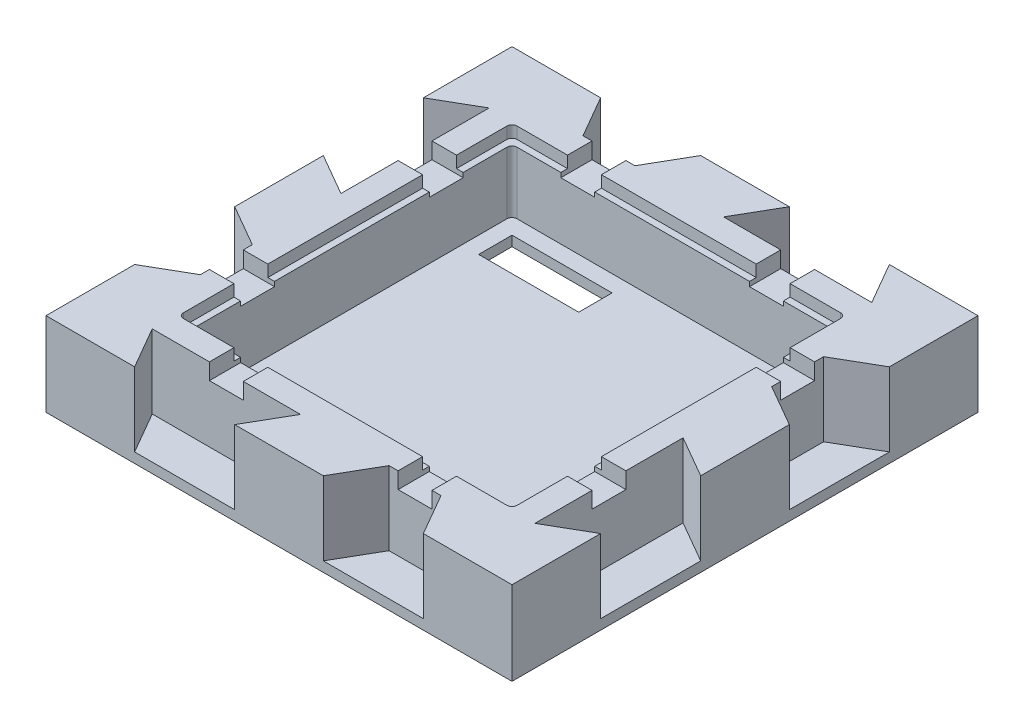
SolidWorks part; units mm, degrees
material "Macor"
ref_plane "Front Plane" through (0, 0, 0) normal (0, 0, 1) x (1, 0, 0)
ref_plane "Top Plane" through (0, 0, 0) normal (0, 1, 0) x (1, 0, 0)
ref_plane "Right Plane" through (0, 0, 0) normal (1, 0, 0) x (0, 0, -1)
sketch "Sketch1" plane through (0, 0, 0) normal (0, 1, 0) x (1, 0, 0)
  line L1 (-69.85, -69.85) -> (69.85, -69.85)
  line L2 (-69.85, -69.85) -> (-69.85, 69.85)
  line L3 (-69.85, 69.85) -> (69.85, 69.85)
  line L4 (69.85, -69.85) -> (69.85, 69.85)
  line L5 (-69.85, -69.85) -> (69.85, 69.85) construction
  line L6 (-69.85, 69.85) -> (69.85, -69.85) construction
  point P0 (0, 0)
  dimension "D1" = 139.7
extrude "Boss-Extrude1" add sketch "Sketch1" along normal mid plane 25.4
sketch "Sketch2" plane through (0, 12.7, 0) normal (0, 1, 0) x (1, 0, 0)
  line L0 (69.85, -69.85) -> (69.85, 69.85) construction
  line L1 (-69.85, -69.85) -> (69.85, -69.85)
  line L2 (-69.85, -69.85) -> (-69.85, 69.85)
  line L3 (-69.85, 69.85) -> (69.85, 69.85)
  line L4 (69.85, -69.85) -> (69.85, 69.85)
  line L5 (-69.85, -69.85) -> (69.85, 69.85) construction
  line L6 (-69.85, 69.85) -> (69.85, -69.85) construction
  point P0 (0, 0)
  dimension "D1" = 0
extrude "Cut-Extrude1" cut sketch "Sketch2" against normal offset from surface (0.3 mm away) 0.3 up to face at (0, 12.7, 0)
sketch "Sketch4" plane through (0, 12.4, 0) normal (0, 1, 0) x (1, 0, 0)
  line L0 (-43.2833, -69.85) -> (-50.5002, -57.35)
  line L2 (-50.5002, -57.35) -> (-6.0665, -57.35)
  line L3 (-6.0665, -57.35) -> (-13.2833, -69.85)
  line L4 (-13.2833, -69.85) -> (-43.2833, -69.85)
  line L5 (43.2833, -69.85) -> (36.0665, -57.35)
  line L24 (43.2833, -69.85) -> (13.2833, -69.85)
  line L25 (-69.85, -69.85) -> (-43.2833, -69.85) construction
  line L26 (-13.2833, -69.85) -> (13.2833, -69.85) construction
  line L27 (43.2833, -69.85) -> (69.85, -69.85) construction
  line L28 (36.0665, -57.35) -> (20.5002, -57.35)
  line L30 (13.2833, -69.85) -> (20.5002, -57.35)
  line L31 (-69.85, 69.85) -> (-69.85, -69.85) construction
  line L32 (69.85, -69.85) -> (69.85, 69.85) construction
  line L33 (-69.85, -69.85) -> (69.85, -69.85) construction
  dimension "D2" = 30
  dimension "D1" = 60
  dimension "D3" = 12.5
  dimension "D4" = 60
extrude "Cut-Extrude2" cut sketch "Sketch4" against normal offset from surface 3 and the other way through all up to face at (0, -12.7, 0)
sketch "Sketch18" plane through (0, 0, 57.35) normal (0, 0, 1) x (1, 0, 0)
  line L1 (0, -13.805) -> (0, 13.805) construction
  line L3 (23.2033, 12.4) -> (23.2033, 7.525)
  line L4 (23.2033, 7.525) -> (33.3633, 7.525)
  line L5 (33.3633, 12.4) -> (33.3633, 7.525)
  line L6 (-23.2033, 12.4) -> (-33.3633, 12.4)
  line L7 (-33.3633, 12.4) -> (-33.3633, 7.525)
  line L8 (-23.2033, 12.4) -> (-23.2033, 7.525)
  line L9 (-23.2033, 7.525) -> (-33.3633, 7.525)
  line L10 (23.2033, 12.4) -> (33.3633, 12.4)
  line L11 (20.5002, 12.4) -> (36.0665, 12.4) construction
  point P7 (28.2833, 12.4)
  point P14 (28.2833, 12.4)
  dimension "D1" = 10.16
  dimension "D2" = 4.875
extrude "Cut-Extrude6" cut sketch "Sketch18" against normal blind 20
ref_axis "Axis1" through (0, 29.6009, 0) along (0, -1, 0)
pattern_circular "CirPattern1" count 4 over 360 about axis through (0, 29.6009, 0) along (0, -1, 0) of "Cut-Extrude2", "Cut-Extrude6"
sketch "Sketch19" plane through (0, 12.4, 0) normal (0, 1, 0) x (1, 0, 0)
  line L1 (-50, -50) -> (50, -50)
  line L2 (-50, -50) -> (-50, 50)
  line L3 (-50, 50) -> (50, 50)
  line L4 (50, -50) -> (50, 50)
  line L5 (-50, -50) -> (50, 50) construction
  line L6 (-50, 50) -> (50, -50) construction
  point P0 (0, 0)
  dimension "D1" = 100
extrude "Cut-Extrude8" cut sketch "Sketch19" against normal blind 3.5
sketch "Sketch20" plane through (0, 8.9, 0) normal (0, 1, 0) x (1, 0, 0)
  line L1 (-48, -48) -> (48, -48)
  line L2 (-48, -48) -> (-48, 48)
  line L3 (-48, 48) -> (48, 48)
  line L4 (48, -48) -> (48, 48)
  line L5 (-48, -48) -> (48, 48) construction
  line L6 (-48, 48) -> (48, -48) construction
  point P0 (0, 0)
  dimension "D1" = 96
extrude "Cut-Extrude9" cut sketch "Sketch20" against normal blind 18.6
sketch "Sketch21" plane through (0, -9.7, 0) normal (0, 1, 0) x (1, 0, 0)
  line L0 (-48, 48) -> (-48, -48) construction
  line L1 (-13, 33) -> (-43, 33)
  line L2 (-13, 33) -> (-13, 43)
  line L3 (-13, 43) -> (-43, 43)
  line L4 (-43, 33) -> (-43, 43)
  line L5 (48, 48) -> (-48, 48) construction
  dimension "D1" = 30
  dimension "D2" = 10
  dimension "D3" = 5
  dimension "D4" = 5
extrude "Cut-Extrude10" cut sketch "Sketch21" against normal through all
fillet "Fillet2" radius 1.5 8 edges at (-50, 10.65, -50) (-50, 10.65, 50) (50, 10.65, 50) (50, 10.65, -50) (48, -0.4, 48) (-48, -0.4, 48) (-48, -0.4, -48) (48, -0.4, -48)
sketch "Sketch22" plane through (0, -12.7, 0) normal (0, -1, 0) x (1, 0, 0)
  line L1 (69.85, -69.85) -> (-69.85, -69.85) construction
  line L2 (-69.85, 69.85) -> (-49.85, 69.85)
  line L3 (-69.85, 69.85) -> (-69.85, -69.85)
  line L4 (-69.85, -69.85) -> (-49.85, -69.85)
  line L5 (-49.85, 69.85) -> (-49.85, -69.85)
  dimension "D1" = 20
split line "Split Line1"
pattern_circular "CirPattern2" count 2 over 360 about axis through (0, 29.6009, 0) along (0, -1, 0) of "Cut-Extrude10"
equation "\"panel_width\"= 5.5in"
equation "\"finger_joint_width\"= 30mm"
equation "\"D1@Sketch1\"=\"panel_width\""
equation "\"D2@Sketch4\"=\"finger_joint_width\""
